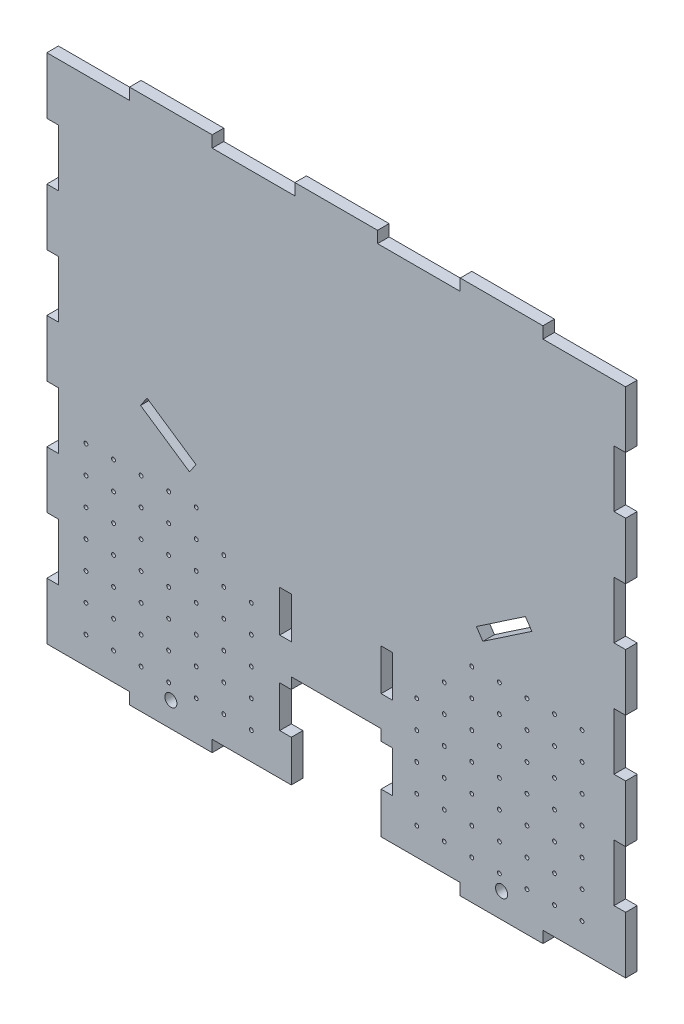
SolidWorks part; units mm, degrees
ref_plane "Front Plane" through (0, 0, 0) normal (0, 0, 1) x (1, 0, 0)
ref_plane "Top Plane" through (0, 0, 0) normal (0, 1, 0) x (1, 0, 0)
ref_plane "Right Plane" through (0, 0, 0) normal (1, 0, 0) x (0, 0, -1)
sketch "Sketch1" plane through (0, 0, 0) normal (0, 0, 1) x (1, 0, 0)
  line L1 (-240.9417, 218.2569) -> (25.7583, 218.2569)
  line L2 (-240.9417, 218.2569) -> (-240.9417, -28.3263)
  line L3 (-240.9417, -28.3263) -> (25.7583, -28.3263)
  line L4 (25.7583, 218.2569) -> (25.7583, -28.3263)
  dimension "D1" = 266.7
  dimension "D2" = 246.5832
extrude "Boss-Extrude1" add sketch "Sketch1" along normal blind 5.334
sketch "Sketch3" plane through (0, 0, 5.334) normal (0, 0, 1) x (1, 0, 0)
  line L0 (25.7583, 218.2569) -> (-240.9417, 218.2569) construction
  line L1 (-240.9417, 218.2569) -> (-202.8417, 218.2569)
  line L2 (-240.9417, 218.2569) -> (-240.9417, 212.9229)
  line L3 (-240.9417, 212.9229) -> (-202.8417, 212.9229)
  line L4 (-202.8417, 218.2569) -> (-202.8417, 212.9229)
  line L5 (-164.7417, 218.2569) -> (-126.6417, 218.2569)
  line L6 (-164.7417, 218.2569) -> (-164.7417, 212.9229)
  line L7 (-164.7417, 212.9229) -> (-126.6417, 212.9229)
  line L8 (-126.6417, 218.2569) -> (-126.6417, 212.9229)
  line L9 (25.7583, -28.3263) -> (25.7583, 218.2569) construction
  line L10 (-88.5417, 218.2569) -> (-50.4417, 218.2569)
  line L11 (-88.5417, 218.2569) -> (-88.5417, 212.9229)
  line L12 (-88.5417, 212.9229) -> (-50.4417, 212.9229)
  line L13 (-50.4417, 218.2569) -> (-50.4417, 212.9229)
  line L14 (-12.3417, 218.2569) -> (25.7583, 218.2569)
  line L15 (-12.3417, 218.2569) -> (-12.3417, 212.9229)
  line L16 (-12.3417, 212.9229) -> (25.7583, 212.9229)
  line L17 (25.7583, 218.2569) -> (25.7583, 212.9229)
  line L18 (-202.8417, 212.9229) -> (-164.7417, 212.9229) construction
  line L19 (-12.3417, 212.9229) -> (-50.4417, 212.9229) construction
  line L20 (-88.5417, 212.9229) -> (-126.6417, 212.9229) construction
  line L21 (-240.9417, 94.9653) -> (25.7583, 94.9653) construction
  line L22 (-240.9417, 218.2569) -> (-240.9417, -28.3263) construction
  line L23 (-88.5417, -22.9923) -> (-126.6417, -22.9923) construction
  line L24 (-12.3417, -22.9923) -> (-50.4417, -22.9923) construction
  line L25 (-202.8417, -22.9923) -> (-164.7417, -22.9923) construction
  line L26 (25.7583, -28.3263) -> (25.7583, -22.9923)
  line L27 (-12.3417, -22.9923) -> (25.7583, -22.9923)
  line L28 (-12.3417, -28.3263) -> (-12.3417, -22.9923)
  line L29 (-12.3417, -28.3263) -> (25.7583, -28.3263)
  line L30 (-50.4417, -28.3263) -> (-50.4417, -22.9923)
  line L31 (-88.5417, -22.9923) -> (-50.4417, -22.9923)
  line L32 (-88.5417, -28.3263) -> (-88.5417, -22.9923)
  line L33 (-88.5417, -28.3263) -> (-50.4417, -28.3263)
  line L34 (-126.6417, -28.3263) -> (-126.6417, -22.9923)
  line L35 (-164.7417, -22.9923) -> (-126.6417, -22.9923)
  line L36 (-164.7417, -28.3263) -> (-164.7417, -22.9923)
  line L37 (-164.7417, -28.3263) -> (-126.6417, -28.3263)
  line L38 (-202.8417, -28.3263) -> (-202.8417, -22.9923)
  line L39 (-240.9417, -22.9923) -> (-202.8417, -22.9923)
  line L40 (-240.9417, -28.3263) -> (-240.9417, -22.9923)
  line L41 (-240.9417, -28.3263) -> (-202.8417, -28.3263)
  dimension "D1" = 5.334
extrude "Cut-Extrude1" cut sketch "Sketch3" against normal through all
sketch "Sketch4" plane through (0, 0, 5.334) normal (0, 0, 1) x (1, 0, 0)
  line L0 (-128.2927, -22.9923) -> (-128.2927, 53.2077) construction
  line L1 (-126.6417, -22.9923) -> (-164.7417, -22.9923) construction
  line L2 (-128.2927, 53.2077) -> (-240.9417, 129.4077) construction
  line L3 (-133.6267, 34.1577) -> (-133.6267, 15.1077) construction
  line L4 (-240.9417, 212.9229) -> (-240.9417, -22.9923) construction
  line L5 (-240.9417, 212.9229) -> (-202.8417, 212.9229) construction
  line L6 (-133.6267, -3.9423) -> (-133.6267, -22.9923) construction
  line L7 (-128.2927, 53.2077) -> (-133.6267, 53.2077)
  line L8 (-128.2927, 53.2077) -> (-128.2927, 34.1577)
  line L9 (-128.2927, 34.1577) -> (-133.6267, 34.1577)
  line L10 (-133.6267, 53.2077) -> (-133.6267, 34.1577)
  line L11 (-128.2927, 15.1077) -> (-133.6267, 15.1077)
  line L12 (-128.2927, 15.1077) -> (-128.2927, -3.9423)
  line L13 (-128.2927, -3.9423) -> (-133.6267, -3.9423)
  line L14 (-133.6267, 15.1077) -> (-133.6267, -3.9423)
  line L15 (-172.2005, 82.9085) -> (-175.1891, 78.4904)
  line L16 (-172.2005, 82.9085) -> (-194.7652, 98.1722)
  line L17 (-175.1891, 78.4904) -> (-197.7538, 93.754)
  line L18 (-194.7652, 98.1722) -> (-197.7538, 93.754)
  line L19 (-107.5917, 218.2569) -> (-107.5917, -28.3263) construction
  line L20 (-88.5417, 218.2569) -> (-126.6417, 218.2569) construction
  line L21 (-126.6417, -28.3263) -> (-88.5417, -28.3263) construction
  line L22 (-81.5567, -3.9423) -> (-81.5567, -22.9923) construction
  line L23 (-81.5567, 34.1577) -> (-81.5567, 15.1077) construction
  line L24 (-86.8907, 53.2077) -> (25.7583, 129.4077) construction
  line L25 (-86.8907, -22.9923) -> (-86.8907, 53.2077) construction
  line L26 (-20.4182, 98.1722) -> (-17.4297, 93.754)
  line L27 (-39.9944, 78.4904) -> (-17.4297, 93.754)
  line L28 (-42.983, 82.9085) -> (-20.4182, 98.1722)
  line L29 (-42.983, 82.9085) -> (-39.9944, 78.4904)
  line L30 (-81.5567, 15.1077) -> (-81.5567, -3.9423)
  line L31 (-86.8907, -3.9423) -> (-81.5567, -3.9423)
  line L32 (-86.8907, 15.1077) -> (-86.8907, -3.9423)
  line L33 (-86.8907, 15.1077) -> (-81.5567, 15.1077)
  line L34 (-81.5567, 53.2077) -> (-81.5567, 34.1577)
  line L35 (-86.8907, 34.1577) -> (-81.5567, 34.1577)
  line L36 (-86.8907, 53.2077) -> (-86.8907, 34.1577)
  line L37 (-86.8907, 53.2077) -> (-81.5567, 53.2077)
  dimension "D1" = 76.2
  dimension "D2" = 76.2
  dimension "D3" = 83.5152
  dimension "D4" = 112.649
  dimension "D5" = 5.334
  dimension "D6" = 5.334
extrude "Cut-Extrude2" cut sketch "Sketch4" against normal through all
sketch "Sketch5" plane through (0, 0, 5.334) normal (0, 0, 1) x (1, 0, 0)
  line L0 (-240.9417, 212.9229) -> (-240.9417, -22.9923) construction
  line L1 (-240.9417, 186.7101) -> (-235.6077, 186.7101)
  line L2 (-240.9417, 186.7101) -> (-240.9417, 160.4973)
  line L3 (-240.9417, 160.4973) -> (-235.6077, 160.4973)
  line L4 (-235.6077, 186.7101) -> (-235.6077, 160.4973)
  line L5 (-235.6077, 186.7101) -> (-235.6077, 212.9229) construction
  line L6 (-240.9417, 134.2845) -> (-235.6077, 134.2845)
  line L7 (-240.9417, 134.2845) -> (-240.9417, 108.0717)
  line L8 (-240.9417, 108.0717) -> (-235.6077, 108.0717)
  line L9 (-235.6077, 134.2845) -> (-235.6077, 108.0717)
  line L10 (-240.9417, 81.8589) -> (-235.6077, 81.8589)
  line L11 (-240.9417, 81.8589) -> (-240.9417, 55.6461)
  line L12 (-240.9417, 55.6461) -> (-235.6077, 55.6461)
  line L13 (-235.6077, 81.8589) -> (-235.6077, 55.6461)
  line L14 (-240.9417, 29.4333) -> (-235.6077, 29.4333)
  line L15 (-240.9417, 29.4333) -> (-240.9417, 3.2205)
  line L16 (-240.9417, 3.2205) -> (-235.6077, 3.2205)
  line L17 (-235.6077, 29.4333) -> (-235.6077, 3.2205)
  line L18 (-240.9417, 212.9229) -> (-202.8417, 212.9229) construction
  line L19 (-235.6077, 160.4973) -> (-235.6077, 134.2845) construction
  line L20 (-235.6077, 108.0717) -> (-235.6077, 81.8589) construction
  line L21 (-235.6077, 55.6461) -> (-235.6077, 29.4333) construction
  line L22 (-235.6077, 3.2205) -> (-235.6077, -22.9923) construction
  line L23 (-202.8417, -22.9923) -> (-240.9417, -22.9923) construction
  line L24 (-107.5917, 218.2569) -> (-107.5917, -28.3263) construction
  line L25 (-88.5417, 218.2569) -> (-126.6417, 218.2569) construction
  line L26 (-126.6417, -28.3263) -> (-88.5417, -28.3263) construction
  line L27 (20.4243, 3.2205) -> (20.4243, -22.9923) construction
  line L28 (20.4243, 55.6461) -> (20.4243, 29.4333) construction
  line L29 (20.4243, 108.0717) -> (20.4243, 81.8589) construction
  line L30 (20.4243, 160.4973) -> (20.4243, 134.2845) construction
  line L31 (20.4243, 186.7101) -> (20.4243, 212.9229) construction
  line L32 (20.4243, 29.4333) -> (20.4243, 3.2205)
  line L33 (25.7583, 3.2205) -> (20.4243, 3.2205)
  line L34 (25.7583, 29.4333) -> (25.7583, 3.2205)
  line L35 (25.7583, 29.4333) -> (20.4243, 29.4333)
  line L36 (20.4243, 81.8589) -> (20.4243, 55.6461)
  line L37 (25.7583, 55.6461) -> (20.4243, 55.6461)
  line L38 (25.7583, 81.8589) -> (25.7583, 55.6461)
  line L39 (25.7583, 81.8589) -> (20.4243, 81.8589)
  line L40 (20.4243, 134.2845) -> (20.4243, 108.0717)
  line L41 (25.7583, 108.0717) -> (20.4243, 108.0717)
  line L42 (25.7583, 134.2845) -> (25.7583, 108.0717)
  line L43 (25.7583, 134.2845) -> (20.4243, 134.2845)
  line L44 (20.4243, 186.7101) -> (20.4243, 160.4973)
  line L45 (25.7583, 160.4973) -> (20.4243, 160.4973)
  line L46 (25.7583, 186.7101) -> (25.7583, 160.4973)
  line L47 (25.7583, 186.7101) -> (20.4243, 186.7101)
  dimension "D1" = 5.334
extrude "Cut-Extrude3" cut sketch "Sketch5" against normal through all
sketch "Sketch6" plane through (0, 0, 5.334) normal (0, 0, 1) x (1, 0, 0)
  line L0 (-202.8417, -22.9923) -> (-240.9417, -22.9923) construction
  line L2 (-235.6077, 3.2205) -> (-235.6077, 29.4333) construction
  line L3 (-222.9077, -10.2923) -> (-210.2077, -10.2923) construction
  circle A0 centre (-222.9077, -10.2923) radius 0.889
  circle A1 centre (-210.2077, -10.2923) radius 0.889
  circle A2 centre (-197.5077, -10.2923) radius 0.889
  circle A3 centre (-184.8077, -10.2923) radius 0.889
  circle A4 centre (-172.1077, -10.2923) radius 0.889
  circle A5 centre (-159.4077, -10.2923) radius 0.889
  circle A6 centre (-146.7077, -10.2923) radius 0.889
  circle A7 centre (-134.0077, -10.2923) radius 0.889 [skipped]
  circle A8 centre (-121.3077, -10.2923) radius 0.889 [skipped]
  circle A9 centre (-108.6077, -10.2923) radius 0.889 [skipped]
  circle A10 centre (-95.9077, -10.2923) radius 0.889 [skipped]
  circle A11 centre (-83.2077, -10.2923) radius 0.889 [skipped]
  circle A12 centre (-70.5077, -10.2923) radius 0.889
  circle A13 centre (-57.8077, -10.2923) radius 0.889
  circle A14 centre (-45.1077, -10.2923) radius 0.889
  circle A15 centre (-32.4077, -10.2923) radius 0.889
  circle A16 centre (-19.7077, -10.2923) radius 0.889
  circle A17 centre (-7.0077, -10.2923) radius 0.889
  circle A18 centre (5.6923, -10.2923) radius 0.889
  circle A19 centre (-210.2077, 2.4077) radius 0.889
  circle A20 centre (-197.5077, 2.4077) radius 0.889
  circle A21 centre (-184.8077, 2.4077) radius 0.889
  circle A22 centre (-172.1077, 2.4077) radius 0.889
  circle A23 centre (-159.4077, 2.4077) radius 0.889
  circle A24 centre (-146.7077, 2.4077) radius 0.889
  circle A25 centre (-134.0077, 2.4077) radius 0.889 [skipped]
  circle A26 centre (-121.3077, 2.4077) radius 0.889 [skipped]
  circle A27 centre (-108.6077, 2.4077) radius 0.889 [skipped]
  circle A28 centre (-95.9077, 2.4077) radius 0.889 [skipped]
  circle A29 centre (-83.2077, 2.4077) radius 0.889 [skipped]
  circle A30 centre (-70.5077, 2.4077) radius 0.889
  circle A31 centre (-57.8077, 2.4077) radius 0.889
  circle A32 centre (-45.1077, 2.4077) radius 0.889
  circle A33 centre (-32.4077, 2.4077) radius 0.889
  circle A34 centre (-19.7077, 2.4077) radius 0.889
  circle A35 centre (-7.0077, 2.4077) radius 0.889
  circle A36 centre (5.6923, 2.4077) radius 0.889
  circle A37 centre (-210.2077, 15.1077) radius 0.889
  circle A38 centre (-197.5077, 15.1077) radius 0.889
  circle A39 centre (-184.8077, 15.1077) radius 0.889
  circle A40 centre (-172.1077, 15.1077) radius 0.889
  circle A41 centre (-159.4077, 15.1077) radius 0.889
  circle A42 centre (-146.7077, 15.1077) radius 0.889
  circle A43 centre (-134.0077, 15.1077) radius 0.889 [skipped]
  circle A44 centre (-121.3077, 15.1077) radius 0.889 [skipped]
  circle A45 centre (-108.6077, 15.1077) radius 0.889 [skipped]
  circle A46 centre (-95.9077, 15.1077) radius 0.889 [skipped]
  circle A47 centre (-83.2077, 15.1077) radius 0.889 [skipped]
  circle A48 centre (-70.5077, 15.1077) radius 0.889
  circle A49 centre (-57.8077, 15.1077) radius 0.889
  circle A50 centre (-45.1077, 15.1077) radius 0.889
  circle A51 centre (-32.4077, 15.1077) radius 0.889
  circle A52 centre (-19.7077, 15.1077) radius 0.889
  circle A53 centre (-7.0077, 15.1077) radius 0.889
  circle A54 centre (5.6923, 15.1077) radius 0.889
  circle A55 centre (-210.2077, 27.8077) radius 0.889
  circle A56 centre (-197.5077, 27.8077) radius 0.889
  circle A57 centre (-184.8077, 27.8077) radius 0.889
  circle A58 centre (-172.1077, 27.8077) radius 0.889
  circle A59 centre (-159.4077, 27.8077) radius 0.889
  circle A60 centre (-146.7077, 27.8077) radius 0.889
  circle A61 centre (-134.0077, 27.8077) radius 0.889 [skipped]
  circle A62 centre (-121.3077, 27.8077) radius 0.889 [skipped]
  circle A63 centre (-108.6077, 27.8077) radius 0.889 [skipped]
  circle A64 centre (-95.9077, 27.8077) radius 0.889 [skipped]
  circle A65 centre (-83.2077, 27.8077) radius 0.889 [skipped]
  circle A66 centre (-70.5077, 27.8077) radius 0.889
  circle A67 centre (-57.8077, 27.8077) radius 0.889
  circle A68 centre (-45.1077, 27.8077) radius 0.889
  circle A69 centre (-32.4077, 27.8077) radius 0.889
  circle A70 centre (-19.7077, 27.8077) radius 0.889
  circle A71 centre (-7.0077, 27.8077) radius 0.889
  circle A72 centre (5.6923, 27.8077) radius 0.889
  circle A73 centre (-210.2077, 40.5077) radius 0.889
  circle A74 centre (-197.5077, 40.5077) radius 0.889
  circle A75 centre (-184.8077, 40.5077) radius 0.889
  circle A76 centre (-172.1077, 40.5077) radius 0.889
  circle A77 centre (-159.4077, 40.5077) radius 0.889
  circle A78 centre (-146.7077, 40.5077) radius 0.889
  circle A79 centre (-134.0077, 40.5077) radius 0.889 [skipped]
  circle A80 centre (-121.3077, 40.5077) radius 0.889 [skipped]
  circle A81 centre (-108.6077, 40.5077) radius 0.889 [skipped]
  circle A82 centre (-95.9077, 40.5077) radius 0.889 [skipped]
  circle A83 centre (-83.2077, 40.5077) radius 0.889 [skipped]
  circle A84 centre (-70.5077, 40.5077) radius 0.889
  circle A85 centre (-57.8077, 40.5077) radius 0.889
  circle A86 centre (-45.1077, 40.5077) radius 0.889
  circle A87 centre (-32.4077, 40.5077) radius 0.889
  circle A88 centre (-19.7077, 40.5077) radius 0.889
  circle A89 centre (-7.0077, 40.5077) radius 0.889
  circle A90 centre (5.6923, 40.5077) radius 0.889
  circle A91 centre (-210.2077, 53.2077) radius 0.889
  circle A92 centre (-197.5077, 53.2077) radius 0.889
  circle A93 centre (-184.8077, 53.2077) radius 0.889
  circle A94 centre (-172.1077, 53.2077) radius 0.889
  circle A95 centre (-159.4077, 53.2077) radius 0.889
  circle A96 centre (-146.7077, 53.2077) radius 0.889 [skipped]
  circle A97 centre (-134.0077, 53.2077) radius 0.889 [skipped]
  circle A98 centre (-121.3077, 53.2077) radius 0.889 [skipped]
  circle A99 centre (-108.6077, 53.2077) radius 0.889 [skipped]
  circle A100 centre (-95.9077, 53.2077) radius 0.889 [skipped]
  circle A101 centre (-83.2077, 53.2077) radius 0.889 [skipped]
  circle A102 centre (-70.5077, 53.2077) radius 0.889 [skipped]
  circle A103 centre (-57.8077, 53.2077) radius 0.889
  circle A104 centre (-45.1077, 53.2077) radius 0.889
  circle A105 centre (-32.4077, 53.2077) radius 0.889
  circle A106 centre (-19.7077, 53.2077) radius 0.889
  circle A107 centre (-7.0077, 53.2077) radius 0.889
  circle A108 centre (5.6923, 53.2077) radius 0.889
  circle A109 centre (-210.2077, 65.9077) radius 0.889
  circle A110 centre (-197.5077, 65.9077) radius 0.889
  circle A111 centre (-184.8077, 65.9077) radius 0.889
  circle A112 centre (-172.1077, 65.9077) radius 0.889
  circle A113 centre (-159.4077, 65.9077) radius 0.889 [skipped]
  circle A114 centre (-146.7077, 65.9077) radius 0.889 [skipped]
  circle A115 centre (-134.0077, 65.9077) radius 0.889 [skipped]
  circle A116 centre (-121.3077, 65.9077) radius 0.889 [skipped]
  circle A117 centre (-108.6077, 65.9077) radius 0.889 [skipped]
  circle A118 centre (-95.9077, 65.9077) radius 0.889 [skipped]
  circle A119 centre (-83.2077, 65.9077) radius 0.889 [skipped]
  circle A120 centre (-70.5077, 65.9077) radius 0.889 [skipped]
  circle A121 centre (-57.8077, 65.9077) radius 0.889 [skipped]
  circle A122 centre (-45.1077, 65.9077) radius 0.889
  circle A123 centre (-32.4077, 65.9077) radius 0.889
  circle A124 centre (-19.7077, 65.9077) radius 0.889
  circle A125 centre (-7.0077, 65.9077) radius 0.889
  circle A126 centre (5.6923, 65.9077) radius 0.889
  circle A127 centre (-222.9077, 2.4077) radius 0.889
  circle A128 centre (-222.9077, 15.1077) radius 0.889
  circle A129 centre (-222.9077, 27.8077) radius 0.889
  circle A130 centre (-222.9077, 40.5077) radius 0.889
  circle A131 centre (-222.9077, 53.2077) radius 0.889
  circle A132 centre (-222.9077, 65.9077) radius 0.889
  dimension "D1" = 12.7
  dimension "D2" = 12.7
  dimension "D6" = 1.778
  dimension "D5" = 12.7
  dimension "D3" = 19
  dimension "D4" = 7
extrude "Cut-Extrude4" cut sketch "Sketch6" against normal through all
sketch "Sketch7" plane through (0, 0, 5.334) normal (0, 0, 1) x (1, 0, 0)
  line L0 (-88.5417, -28.3263) -> (-50.4417, -28.3263) construction
  line L2 (-164.7417, -28.3263) -> (-126.6417, -28.3263) construction
  line L3 (-128.2927, 0) -> (-128.2927, -28.3263) construction
  line L4 (-128.2927, -3.9423) -> (-128.2927, 15.1077) construction
  line L5 (-86.8907, 0) -> (-86.8907, -28.3263) construction
  line L6 (-86.8907, 15.1077) -> (-86.8907, -3.9423) construction
  line L8 (-128.2927, -28.3263) -> (-86.8907, -28.3263)
  line L9 (-128.2927, -28.3263) -> (-128.2927, 20.1877)
  line L10 (-128.2927, 20.1877) -> (-86.8907, 20.1877)
  line L11 (-86.8907, -28.3263) -> (-86.8907, 20.1877)
  dimension "D1" = 48.514
extrude "Cut-Extrude5" cut sketch "Sketch7" against normal through all
sketch "Sketch8" plane through (0, 0, 5.334) normal (0, 0, 1) x (1, 0, 0)
  line L0 (-202.8417, -28.3263) -> (-164.7417, -28.3263) construction
  line L1 (-164.7417, -27.1144) -> (-202.8417, -27.1144) construction
  line L2 (-164.7417, -22.9923) -> (-164.7417, -28.3263) construction
  line L3 (-202.8417, -28.3263) -> (-202.8417, -22.9923) construction
  line L4 (-183.7917, -27.1144) -> (-183.7917, -12.5958) construction
  line L5 (-107.5917, 20.1877) -> (-107.5917, 125.8068) construction
  line L6 (-86.8907, 20.1877) -> (-128.2927, 20.1877) construction
  circle A0 centre (-183.7917, -16.8963) radius 2.794
  circle A1 centre (-31.3917, -16.8963) radius 2.794
  dimension "D1" = 5.588
  dimension "D2" = 11.43
  dimension "D3" = 0
extrude "Cut-Extrude6" cut sketch "Sketch8" against normal through all
equation "\"MDF\"= .21in"
equation "\"Foamcore\"= .13in"
equation "\"Gmaterial\"= \"MDF\""
equation "\"D1@Boss-Extrude1\"=\"MDF\""
equation "\"D1@Sketch3\"=\"MDF\""
equation "\"D5@Sketch4\"=\"MDF\""
equation "\"D6@Sketch4\"=\"MDF\""
equation "\"D1@Sketch5\"=\"MDF\""
equation "\"D1@Sketch7\"=\"MDF\"+1.7"
